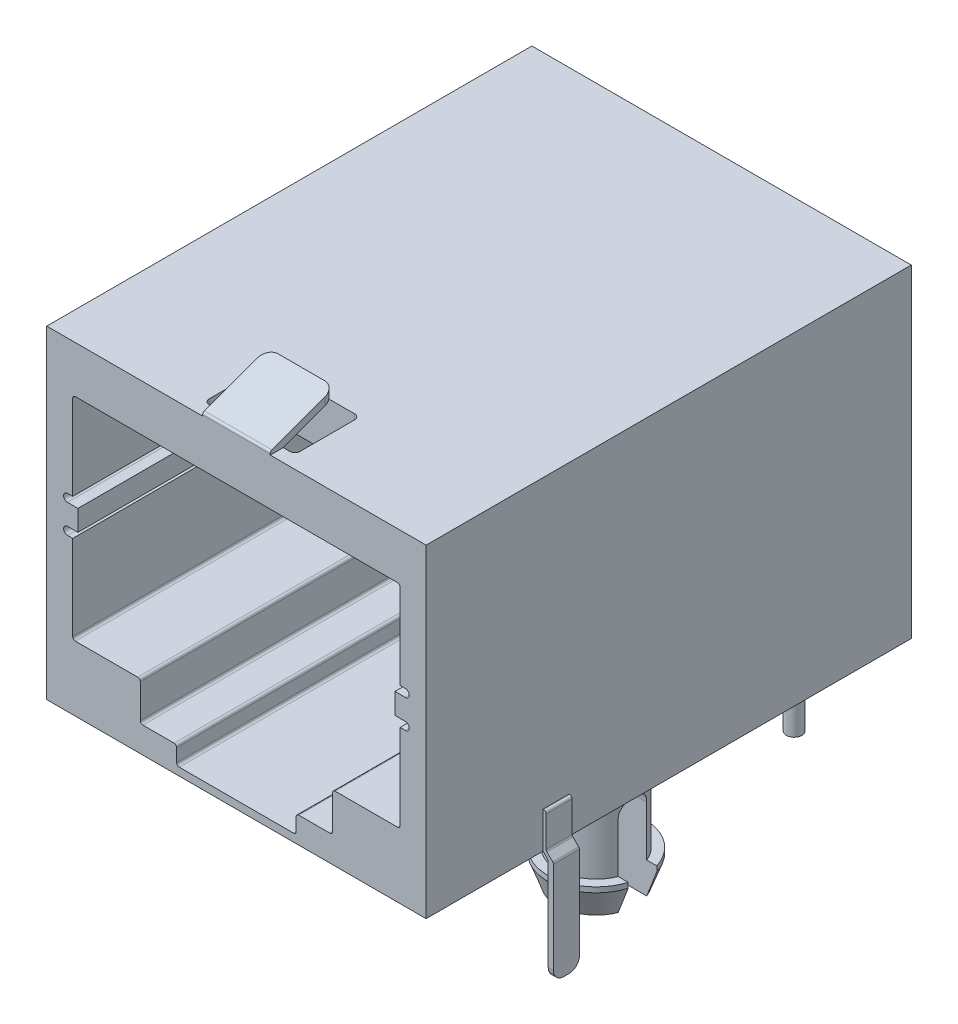
SolidWorks part; units mm, degrees
ref_plane "Plano frontal" through (0, 0, 0) normal (0, 0, 1) x (1, 0, 0)
ref_plane "Plano superior" through (0, 0, 0) normal (0, 1, 0) x (1, 0, 0)
ref_plane "Plano direito" through (0, 0, 0) normal (1, 0, 0) x (0, 0, -1)
sketch "Esboço1" plane through (0, 0, 0) normal (0, 0, 1) x (1, 0, 0)
  line L0 (0, 36.8425) -> (0, 0) construction
  line L2 (-7.3, 12.95) -> (7.3, 12.95)
  line L3 (-7.3, 12.95) -> (-7.3, 0.5)
  line L4 (-7.3, 0.5) -> (7.3, 0.5)
  line L5 (7.3, 12.95) -> (7.3, 0.5)
  line L6 (-7.3, 12.95) -> (7.3, 0.5) construction
  line L7 (-7.3, 0.5) -> (7.3, 12.95) construction
  point P3 (0, 6.725)
  dimension "D1" = 0.5
  dimension "D2" = 12.45
  dimension "D3" = 14.6
extrude "Ressalto-extrusão1" add sketch "Esboço1" along normal blind 9.335 and the other way blind 9.335
sketch "Esboço2" plane through (0, 0, 9.335) normal (0, 0, 1) x (1, 0, 0)
  line L0 (0, 12.95) -> (0, 0.5) construction
  line L1 (7.3, 12.95) -> (-7.3, 12.95) construction
  line L2 (-7.3, 0.5) -> (7.3, 0.5) construction
  line L3 (6.2, 11.15) -> (-6.2, 11.15)
  line L4 (-6.3, 11.15) -> (-6.3, 3) construction
  line L5 (-6.3, 7.075) -> (-2.7204, 7.075) construction
  line L6 (-6.3, 11.05) -> (-6.3, 7.775)
  line L7 (-6.3, 7.775) -> (-6.5, 7.775)
  line L8 (-6.5, 7.775) -> (-6.5, 7.475) construction
  line L9 (-6.2, 3) -> (-3.8, 3)
  line L10 (-3.7, 2.9) -> (-3.7, 1.6)
  line L11 (-3.6, 1.5) -> (-2.4, 1.5)
  line L12 (-2.3, 1.4) -> (-2.3, 0.9)
  line L13 (-2.2, 0.8) -> (2.2, 0.8)
  line L14 (-6.5, 7.475) -> (-6.1, 7.475)
  line L15 (-6.1, 7.475) -> (-6.1, 6.675)
  line L16 (-7.3, 12.95) -> (-7.3, 0.5) construction
  line L17 (-6.3, 3.1) -> (-6.3, 6.375)
  line L18 (-6.5, 6.675) -> (-6.1, 6.675)
  line L19 (-6.3, 6.375) -> (-6.5, 6.375)
  line L20 (6.5, 7.775) -> (6.5, 7.475) construction
  line L21 (6.3, 7.075) -> (2.7204, 7.075) construction
  line L22 (6.3, 11.15) -> (6.3, 3) construction
  line L23 (6.3, 6.375) -> (6.5, 6.375)
  line L24 (6.5, 6.675) -> (6.1, 6.675)
  line L25 (6.3, 3.1) -> (6.3, 6.375)
  line L26 (6.1, 7.475) -> (6.1, 6.675)
  line L27 (6.5, 7.475) -> (6.1, 7.475)
  line L28 (2.3, 1.4) -> (2.3, 0.9)
  line L29 (3.6, 1.5) -> (2.4, 1.5)
  line L30 (3.7, 2.9) -> (3.7, 1.6)
  line L31 (6.2, 3) -> (3.8, 3)
  line L32 (6.3, 7.775) -> (6.5, 7.775)
  line L33 (6.3, 11.05) -> (6.3, 7.775)
  arc A0 (-6.5, 7.775) -> (-6.5, 7.475) centre (-6.5, 7.625) ccw
  arc A1 (-6.5, 6.375) -> (-6.5, 6.675) centre (-6.5, 6.525) cw
  arc A2 (-2.3, 0.9) -> (-2.2, 0.8) centre (-2.2, 0.9) ccw
  arc A3 (-2.4, 1.5) -> (-2.3, 1.4) centre (-2.4, 1.4) cw
  arc A4 (-3.7, 1.6) -> (-3.6, 1.5) centre (-3.6, 1.6) ccw
  arc A5 (-3.8, 3) -> (-3.7, 2.9) centre (-3.8, 2.9) cw
  arc A6 (-6.3, 3.1) -> (-6.2, 3) centre (-6.2, 3.1) ccw
  arc A7 (-6.2, 11.15) -> (-6.3, 11.05) centre (-6.2, 11.05) ccw
  arc A8 (6.2, 11.15) -> (6.3, 11.05) centre (6.2, 11.05) cw
  arc A9 (6.3, 3.1) -> (6.2, 3) centre (6.2, 3.1) cw
  arc A10 (3.8, 3) -> (3.7, 2.9) centre (3.8, 2.9) ccw
  arc A11 (3.7, 1.6) -> (3.6, 1.5) centre (3.6, 1.6) cw
  arc A12 (2.4, 1.5) -> (2.3, 1.4) centre (2.4, 1.4) ccw
  arc A13 (2.3, 0.9) -> (2.2, 0.8) centre (2.2, 0.9) cw
  arc A14 (6.5, 6.375) -> (6.5, 6.675) centre (6.5, 6.525) ccw
  arc A15 (6.5, 7.775) -> (6.5, 7.475) centre (6.5, 7.625) cw
  point P6 (3.7, 1.5)
  point P25 (-6.5, 6.525)
  point P30 (-6.1, 7.075)
  point P34 (-2.3, 1.5)
  point P37 (-3.7, 1.5)
  point P77 (0, 0.8)
  point P78 (0, 11.15)
  point P79 (2.3, 1.5)
  point P80 (6.1, 7.075)
  dimension "D11" = 0.1
  dimension "D1" = 0.3
  dimension "D2" = 0.4
  dimension "D3" = 1.8
  dimension "D4" = 1
  dimension "D5" = 0.2
  dimension "D6" = 0.2
  dimension "D7" = 2.5
  dimension "D8" = 2.6
  dimension "D9" = 1.4
  dimension "D10" = 1
  dimension "D12" = 0.3
extrude "Corte-extrusão1" cut sketch "Esboço2" against normal blind 13
sketch "Esboço3" plane through (0, 0.5, 0) normal (0, -1, 0) x (1, 0, 0)
  line L0 (0, 9.335) -> (0, -9.335) construction
  line L1 (-7.3, 9.335) -> (7.3, 9.335) construction
  line L2 (-7.3, -9.335) -> (7.3, -9.335) construction
  circle A0 centre (-5.715, 1.205) radius 1.5
  circle A1 centre (-4.445, -5.145) radius 0.3
  circle A2 centre (-3.175, -7.685) radius 0.3
  circle A3 centre (5.715, 1.205) radius 1.5
  circle A4 centre (-1.905, -5.145) radius 0.3
  circle A5 centre (-0.635, -7.685) radius 0.3
  circle A6 centre (0.635, -5.145) radius 0.3
  circle A7 centre (1.905, -7.685) radius 0.3
  circle A8 centre (3.175, -5.145) radius 0.3
  circle A9 centre (4.445, -7.685) radius 0.3
  dimension "D1" = 0.6
  dimension "D2" = 0.6
  dimension "D9" = 3
  dimension "D3" = 1.27
  dimension "D4" = 1.27
  dimension "D5" = 5.715
  dimension "D6" = 8.13
  dimension "D7" = 6.35
  dimension "D8" = 2.54
  dimension "D10" = 4
extrude "Ressalto-extrusão2" add sketch "Esboço3" along normal blind 3.68
sketch "Esboço4" plane through (0, -3.18, 0) normal (0, -1, 0) x (1, 0, 0)
  circle A0 centre (-5.715, 1.205) radius 1.5 construction
  circle A1 centre (5.715, 1.205) radius 1.5 construction
  circle A2 centre (-5.715, 1.205) radius 1.5
  circle A3 centre (5.715, 1.205) radius 1.5
extrude "Ressalto-extrusão3" add sketch "Esboço4" against normal blind 1 draft 20 draft outward yes
sketch "Esboço5" plane through (0, -2.18, 0) normal (0, 1, 0) x (1, 0, 0)
  circle A0 centre (-5.715, -1.205) radius 1.864 construction
  circle A1 centre (5.715, -1.205) radius 1.864 construction
  circle A2 centre (-5.715, -1.205) radius 1.864
  circle A3 centre (5.715, -1.205) radius 1.864
extrude "Ressalto-extrusão4" add sketch "Esboço5" along normal blind 0.2
sketch "Esboço7" plane through (0, 0.5, 0) normal (0, -1, 0) x (1, 0, 0)
  line L0 (0, 9.335) -> (0, -9.335) construction
  line L1 (-7.3, 9.335) -> (7.3, 9.335) construction
  line L2 (-7.3, -9.335) -> (7.3, -9.335) construction
  line L3 (-3.175, -7.985) -> (-3.175, 9.335) construction
  line L4 (-3.175, -7.985) -> (-3.175, -9.335) construction
  line L5 (-3.825, 7.1522) -> (-2.525, 7.1522)
  line L6 (-3.825, 7.1522) -> (-3.825, 2.6522)
  line L7 (-3.825, 2.6522) -> (-2.525, 2.6522)
  line L8 (-2.525, 7.1522) -> (-2.525, 2.6522)
  line L9 (-3.825, 7.1522) -> (-2.525, 2.6522) construction
  line L10 (-3.825, 2.6522) -> (-2.525, 7.1522) construction
  line L11 (-3.825, -8.2792) -> (-2.525, -8.2792)
  line L12 (-3.825, -8.2792) -> (-3.825, -9.1461)
  line L13 (-3.825, -9.1461) -> (-2.525, -9.1461)
  line L14 (-2.525, -8.2792) -> (-2.525, -9.1461)
  line L15 (-3.825, -8.2792) -> (-2.525, -9.1461) construction
  line L16 (-3.825, -9.1461) -> (-2.525, -8.2792) construction
  line L17 (3.825, -9.1461) -> (2.525, -8.2792) construction
  line L18 (3.825, -8.2792) -> (2.525, -9.1461) construction
  line L19 (3.825, 2.6522) -> (2.525, 7.1522) construction
  line L20 (3.825, 7.1522) -> (2.525, 2.6522) construction
  line L21 (3.175, -7.985) -> (3.175, -9.335) construction
  line L22 (3.175, -7.985) -> (3.175, 9.335) construction
  line L23 (2.525, -8.2792) -> (2.525, -9.1461)
  line L24 (3.825, -9.1461) -> (2.525, -9.1461)
  line L25 (3.825, -8.2792) -> (3.825, -9.1461)
  line L26 (3.825, -8.2792) -> (2.525, -8.2792)
  line L27 (2.525, 7.1522) -> (2.525, 2.6522)
  line L28 (3.825, 2.6522) -> (2.525, 2.6522)
  line L29 (3.825, 7.1522) -> (3.825, 2.6522)
  line L30 (3.825, 7.1522) -> (2.525, 7.1522)
  circle A0 centre (-3.175, -7.685) radius 0.3 construction
  circle A1 centre (-3.175, -7.685) radius 0.3 construction
  point P12 (-3.175, 4.9022)
  point P18 (-3.175, -8.7126)
  point P35 (3.175, -8.7126)
  point P36 (3.175, 4.9022)
  dimension "D1" = 2.1828
  dimension "D2" = 1.3
  dimension "D3" = 4.5
  dimension "D4" = 1.3
extrude "Ressalto-extrusão5" add sketch "Esboço7" along normal blind 0.5
sketch "Esboço8" plane through (7.3, 0, 0) normal (1, 0, 0) x (0, 0, -1)
  line L0 (-1.205, -3.18) -> (-1.205, 4.3732) construction
  line L1 (-2.705, -3.18) -> (0.295, -3.18) construction
  line L2 (-1.755, -0.05) -> (-1.755, -3.18)
  line L3 (-0.655, -0.05) -> (-0.655, -3.18)
  line L4 (9.335, 0.5) -> (-9.335, 0.5) construction
  line L5 (-1.755, -3.18) -> (-0.655, -3.18)
  arc A0 (-0.655, -0.05) -> (-1.755, -0.05) centre (-1.205, -0.05) ccw
  dimension "D1" = 1.1
extrude "Corte-extrusão2" cut sketch "Esboço8" against normal through all and the other way through all
ref_plane "Plano2" through (0, 0, 4.335) normal (0, 0, 1) x (1, 0, 0)
sketch "Esboço9" plane through (0, 0, 4.335) normal (0, 0, 1) x (1, 0, 0)
  line L0 (-7.3, 1.9) -> (-7.32, 1.9)
  line L1 (-7.3, 12.95) -> (-7.3, 0.5) construction
  line L2 (-7.42, 1.8) -> (-7.42, 0.6214)
  line L3 (-7.4493, 0.5507) -> (-7.6707, 0.3293)
  line L4 (-7.7, 0.2586) -> (-7.7, -3.68)
  line L5 (-7.7, -3.68) -> (-7.5, -3.68)
  line L6 (-7.5, -3.68) -> (-7.5, 0.2586)
  line L7 (-7.4707, 0.3293) -> (-7.3, 0.5)
  line L8 (-7.6, -3.68) -> (-7.6, -2.2361) construction
  line L9 (-7.3, 1.9) -> (-7.3, 0.5)
  line L10 (-7.215, 0.5) -> (-4.215, 0.5) construction
  line L11 (-7.1105, -3.18) -> (-4.3195, -3.18) construction
  line L12 (0, 4.2672) -> (0, -7.912) construction
  line L13 (7.6, -3.68) -> (7.6, -2.2361) construction
  line L14 (7.3, 1.9) -> (7.3, 0.5)
  line L15 (7.4707, 0.3293) -> (7.3, 0.5)
  line L16 (7.5, -3.68) -> (7.5, 0.2586)
  line L17 (7.7, -3.68) -> (7.5, -3.68)
  line L18 (7.7, 0.2586) -> (7.7, -3.68)
  line L19 (7.4493, 0.5507) -> (7.6707, 0.3293)
  line L20 (7.42, 1.8) -> (7.42, 0.6214)
  line L21 (7.3, 1.9) -> (7.32, 1.9)
  arc A0 (-7.5, 0.2586) -> (-7.4707, 0.3293) centre (-7.4, 0.2586) cw
  arc A1 (-7.6707, 0.3293) -> (-7.7, 0.2586) centre (-7.6, 0.2586) ccw
  arc A2 (-7.42, 0.6214) -> (-7.4493, 0.5507) centre (-7.52, 0.6214) cw
  arc A3 (-7.32, 1.9) -> (-7.42, 1.8) centre (-7.32, 1.8) ccw
  arc A4 (7.32, 1.9) -> (7.42, 1.8) centre (7.32, 1.8) cw
  arc A5 (7.42, 0.6214) -> (7.4493, 0.5507) centre (7.52, 0.6214) ccw
  arc A6 (7.6707, 0.3293) -> (7.7, 0.2586) centre (7.6, 0.2586) cw
  arc A7 (7.5, 0.2586) -> (7.4707, 0.3293) centre (7.4, 0.2586) ccw
  point P20 (-7.5, 0.3)
  point P23 (-7.7, 0.3)
  point P28 (-7.42, 1.9)
  point P49 (7.42, 1.9)
  point P50 (7.7, 0.3)
  point P51 (7.5, 0.3)
  dimension "D7" = 0.1
  dimension "D1" = 135
  dimension "D2" = 7.6
  dimension "D3" = 0.12
  dimension "D4" = 0.5
  dimension "D5" = 1.4
extrude "Ressalto-extrusão6" add sketch "Esboço9" along normal blind 0.5 and the other way blind 0.5
fillet "Filete1" radius 0.4 4 edges at (-7.6, -3.68, 4.835) (-7.6, -3.68, 3.835) (7.6, -3.68, 3.835) (7.6, -3.68, 4.835)
sketch "Esboço11" plane through (0, 0, -3.665) normal (0, 0, 1) x (1, 0, 0)
  line L0 (0, 12.95) -> (0, 0.5) construction
  line L1 (7.3, 12.95) -> (-7.3, 12.95) construction
  line L2 (-7.3, 0.5) -> (7.3, 0.5) construction
  line L3 (6.2, 11.15) -> (-6.2, 11.15) construction
  line L4 (-0.25, 11.15) -> (-0.75, 11.15)
  line L5 (-0.25, 11.15) -> (-0.25, 7.075)
  line L6 (-0.25, 7.075) -> (-0.75, 7.075)
  line L7 (-0.75, 11.15) -> (-0.75, 7.075)
  line L8 (-0.5, 7.075) -> (-0.5, 11.15) construction
  line L9 (-6.1, 7.075) -> (6.1, 7.075) construction
  line L10 (-6.1, 7.475) -> (-6.1, 6.675) construction
  line L11 (6.1, 6.675) -> (6.1, 7.475) construction
  line L12 (0.75, 11.15) -> (0.25, 11.15)
  line L13 (0.75, 11.15) -> (0.75, 7.075)
  line L14 (0.75, 7.075) -> (0.25, 7.075)
  line L15 (0.25, 11.15) -> (0.25, 7.075)
  line L16 (0.5, 7.075) -> (0.5, 11.15) construction
  line L17 (1.75, 11.15) -> (1.25, 11.15)
  line L18 (1.75, 11.15) -> (1.75, 7.075)
  line L19 (1.75, 7.075) -> (1.25, 7.075)
  line L20 (1.25, 11.15) -> (1.25, 7.075)
  line L21 (1.5, 7.075) -> (1.5, 11.15) construction
  line L22 (2.75, 11.15) -> (2.25, 11.15)
  line L23 (2.75, 11.15) -> (2.75, 7.075)
  line L24 (2.75, 7.075) -> (2.25, 7.075)
  line L25 (2.25, 11.15) -> (2.25, 7.075)
  line L26 (2.5, 7.075) -> (2.5, 11.15) construction
  line L27 (3.75, 11.15) -> (3.25, 11.15)
  line L28 (3.75, 11.15) -> (3.75, 7.075)
  line L29 (3.75, 7.075) -> (3.25, 7.075)
  line L30 (3.25, 11.15) -> (3.25, 7.075)
  line L31 (3.5, 7.075) -> (3.5, 11.15) construction
  line L32 (-1.25, 11.15) -> (-1.75, 11.15)
  line L33 (-1.25, 11.15) -> (-1.25, 7.075)
  line L34 (-1.25, 7.075) -> (-1.75, 7.075)
  line L35 (-1.75, 11.15) -> (-1.75, 7.075)
  line L36 (-1.5, 7.075) -> (-1.5, 11.15) construction
  line L37 (-2.25, 11.15) -> (-2.75, 11.15)
  line L38 (-2.25, 11.15) -> (-2.25, 7.075)
  line L39 (-2.25, 7.075) -> (-2.75, 7.075)
  line L40 (-2.75, 11.15) -> (-2.75, 7.075)
  line L41 (-2.5, 7.075) -> (-2.5, 11.15) construction
  line L42 (-3.25, 11.15) -> (-3.75, 11.15)
  line L43 (-3.25, 11.15) -> (-3.25, 7.075)
  line L44 (-3.25, 7.075) -> (-3.75, 7.075)
  line L45 (-3.75, 11.15) -> (-3.75, 7.075)
  line L46 (-3.5, 7.075) -> (-3.5, 11.15) construction
  dimension "D1" = 0.5
  dimension "D2" = 0.5
  dimension "D3" = 5
  dimension "D4" = 4
extrude "Ressalto-extrusão7" add sketch "Esboço11" along normal blind 3
chamfer "Chanfro1" distance 2 angle 45 8 edges at (3.5, 7.075, -0.665) (2.5, 7.075, -0.665) (1.5, 7.075, -0.665) (0.5, 7.075, -0.665) (-0.5, 7.075, -0.665) (-1.5, 7.075, -0.665) (-2.5, 7.075, -0.665) (-3.5, 7.075, -0.665)
sketch "Esboço12" plane through (0, 12.95, 0) normal (0, 1, 0) x (1, 0, 0)
  line L0 (0, -9.335) -> (0, -1.7772) construction
  line L1 (7.3, -9.335) -> (-7.3, -9.335) construction
  line L3 (-1.55, -6.335) -> (1.55, -6.335)
  line L4 (-1.75, -6.535) -> (-1.75, -8.635)
  line L5 (-1.55, -8.835) -> (1.55, -8.835)
  line L6 (1.75, -6.535) -> (1.75, -8.635)
  line L7 (-1.75, -6.335) -> (1.75, -8.835) construction
  line L8 (-1.75, -8.835) -> (1.75, -6.335) construction
  arc A0 (1.55, -6.335) -> (1.75, -6.535) centre (1.55, -6.535) cw
  arc A1 (1.55, -8.835) -> (1.75, -8.635) centre (1.55, -8.635) ccw
  arc A2 (-1.75, -8.635) -> (-1.55, -8.835) centre (-1.55, -8.635) ccw
  arc A3 (-1.55, -6.335) -> (-1.75, -6.535) centre (-1.55, -6.535) ccw
  point P5 (0, -7.585)
  dimension "D4" = 0.2
  dimension "D1" = 0.5
  dimension "D2" = 2.5
  dimension "D3" = 3.5
extrude "Corte-extrusão3" cut sketch "Esboço12" against normal up to next
sketch "Esboço13" plane through (0, 0, 0) normal (1, 0, 0) x (0, 0, -1)
  line L0 (-9.2692, 13.092) -> (-6.835, 13.9779)
  line L1 (-6.835, 13.9779) -> (-6.835, 13.6779)
  line L2 (-6.835, 13.6779) -> (-8.835, 12.95)
  line L3 (9.335, 12.95) -> (-9.335, 12.95) construction
  line L4 (-9.335, 0.5) -> (-9.335, 12.95) construction
  line L5 (-9.335, 12.95) -> (-9.335, 12.998)
  line L6 (-9.335, 12.95) -> (-8.835, 12.95)
  arc A0 (-9.2692, 13.092) -> (-9.335, 12.998) centre (-9.235, 12.998) ccw
  point P12 (-9.335, 13.068)
  dimension "D5" = 0.1
  dimension "D1" = 0.5
  dimension "D2" = 20
  dimension "D3" = 2.5
  dimension "D4" = 0.3
extrude "Ressalto-extrusão8" add sketch "Esboço13" along normal blind 1.3 and the other way blind 1.3
fillet "Filete2" radius 0.4 2 edges at (-1.3, 13.8279, 6.835) (1.3, 13.8279, 6.835)
